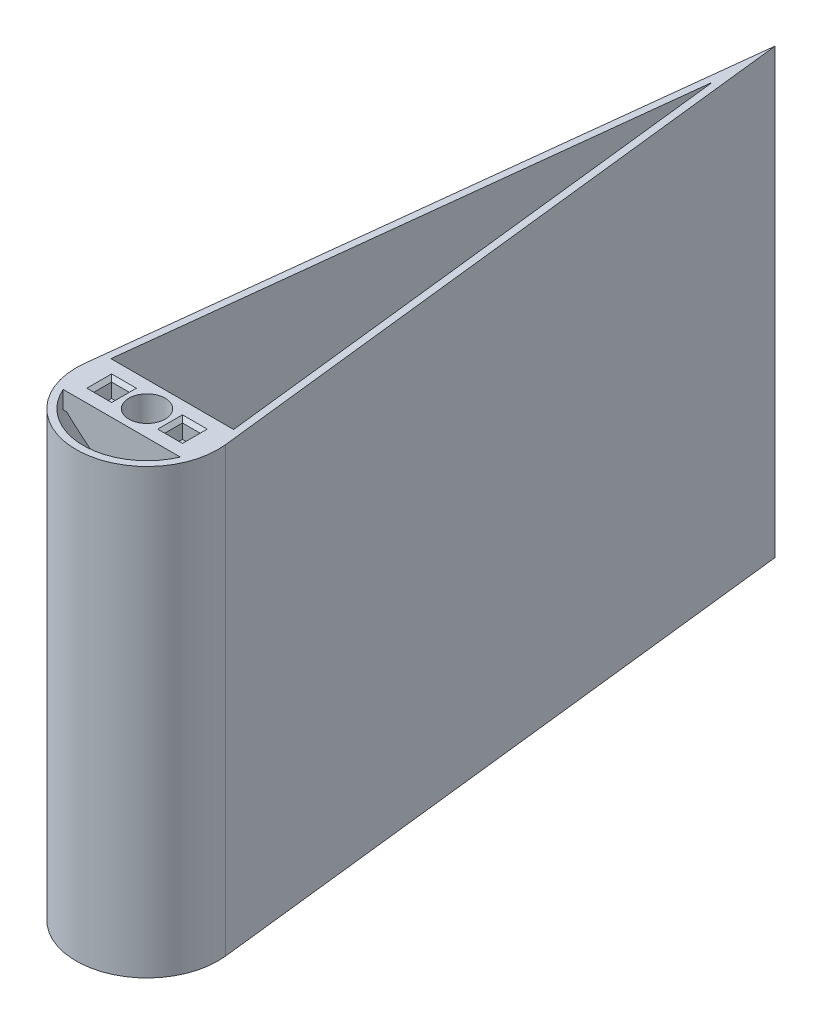
SolidWorks part; units mm, degrees
material "ABS"
ref_plane "Front Plane" through (0, 0, 0) normal (0, 0, 1) x (1, 0, 0)
ref_plane "Top Plane" through (0, 0, 0) normal (0, 1, 0) x (1, 0, 0)
ref_plane "Right Plane" through (0, 0, 0) normal (1, 0, 0) x (0, 0, -1)
sketch "Sketch1" plane through (0, 0, 0) normal (0, 1, 0) x (1, 0, 0)
  line L0 (-19.8723, 2.2566) -> (0, 177.2566)
  line L1 (0, 177.2566) -> (19.8723, 2.2566)
  arc A0 (-19.8723, 2.2566) -> (19.8723, 2.2566) centre (0, 0) ccw
  circle A1 centre (0, 0) radius 5.125
  dimension "D1" = 10.25
  dimension "D2" = 20
  dimension "D3" = 175
extrude "Boss-Extrude1" add sketch "Sketch1" along normal blind 125
sketch "Sketch2" plane through (0, 0, 0) normal (0, -1, 0) x (1, 0, 0)
  line L0 (12.5, 2.5) -> (7.5, 2.5)
  line L1 (-2.5, 12.5) -> (2.5, 12.5)
  line L2 (-2.5, 12.5) -> (-2.5, 7.5)
  line L3 (-2.5, 7.5) -> (2.5, 7.5)
  line L4 (2.5, 12.5) -> (2.5, 7.5)
  line L5 (-2.5, 12.5) -> (2.5, 7.5) construction
  line L6 (-2.5, 7.5) -> (2.5, 12.5) construction
  line L7 (12.5, 2.5) -> (12.5, -2.5)
  line L8 (12.5, -2.5) -> (7.5, -2.5)
  line L9 (7.5, 2.5) -> (7.5, -2.5)
  line L10 (2.5, -12.5) -> (2.5, -7.5)
  line L11 (2.5, -12.5) -> (-2.5, -12.5)
  line L12 (-2.5, -12.5) -> (-2.5, -7.5)
  line L13 (2.5, -7.5) -> (-2.5, -7.5)
  line L14 (-12.5, -2.5) -> (-7.5, -2.5)
  line L15 (-12.5, -2.5) -> (-12.5, 2.5)
  line L16 (-12.5, 2.5) -> (-7.5, 2.5)
  line L17 (-7.5, -2.5) -> (-7.5, 2.5)
  point P0 (0, 10)
  point P21 (0, 0)
  dimension "D1" = 5
  dimension "D2" = 5
  dimension "D3" = 10
  dimension "D4" = 4
extrude "Cut-Extrude1" cut sketch "Sketch2" against normal blind 5
shell "Shell1" thickness 2 removed face at (0, 125, -53.1711)
fillet "Fillet1" radius 5 4 edges at (5.0381, 2, 5.0381) (-5.0381, 2, 5.0381) (-5.0381, 2, -5.0381) (5.0381, 2, -5.0381)
sketch "Sketch3" plane through (0, 125, 0) normal (0, 1, 0) x (1, 0, 0)
  line L0 (0, 159.531) -> (-17.8851, 2.031) construction
  line L5 (17.8851, 2.031) -> (0, 159.531) construction
  line L6 (-16.5298, -7.125) -> (16.5298, -7.125)
  line L7 (-17.3066, 7.125) -> (-17.8851, 2.031)
  line L10 (17.8851, 2.031) -> (17.3066, 7.125)
  line L14 (-17.3066, 7.125) -> (17.3066, 7.125)
  arc A1 (-17.8851, 2.031) -> (17.8851, 2.031) centre (0, 0) ccw construction
  circle A2 centre (0, 0) radius 7.125 construction
  arc A3 (-17.8851, 2.031) -> (-16.5298, -7.125) centre (0, 0) ccw
  arc A4 (16.5298, -7.125) -> (17.8851, 2.031) centre (0, 0) ccw
  arc A5 (-4.5, -5.5241) -> (4.5, -5.5241) centre (0, 0) ccw construction
  circle A6 centre (0, 0) radius 5.125 construction
  circle A7 centre (0, 0) radius 5.125
  point P0 (0, 0)
extrude "Boss-Extrude2" add sketch "Sketch3" against normal blind 5
chamfer "Chamfer1" distance 10 angle 45 2 edges at (7.125, 120, 0) (-7.125, 120, 0)
sketch "Sketch5" plane through (0, 125, 0) normal (0, 1, 0) x (1, 0, 0)
  line L0 (12.5, -2.5) -> (12.5, 2.5)
  line L1 (-12.5, 2.5) -> (-7.5, 2.5)
  line L2 (-12.5, 2.5) -> (-12.5, -2.5)
  line L3 (-12.5, -2.5) -> (-7.5, -2.5)
  line L4 (-7.5, 2.5) -> (-7.5, -2.5)
  line L5 (-12.5, 2.5) -> (-7.5, -2.5) construction
  line L6 (-12.5, -2.5) -> (-7.5, 2.5) construction
  line L7 (12.5, -2.5) -> (7.5, -2.5)
  line L8 (7.5, -2.5) -> (7.5, 2.5)
  line L9 (12.5, 2.5) -> (7.5, 2.5)
  point P0 (-10, 0)
  point P13 (0, 0)
  dimension "D1" = 5
  dimension "D2" = 5
  dimension "D3" = 10
  dimension "D4" = 2
extrude "Cut-Extrude3" cut sketch "Sketch5" against normal blind 5
chamfer "Chamfer2" distance 1 angle 45 8 edges at (12.5, 125, 0) (10, 125, -2.5) (10, 125, 2.5) (7.5, 125, 0) (-10, 125, 2.5) (-7.5, 125, 0) (-12.5, 125, 0) (-10, 125, -2.5)
